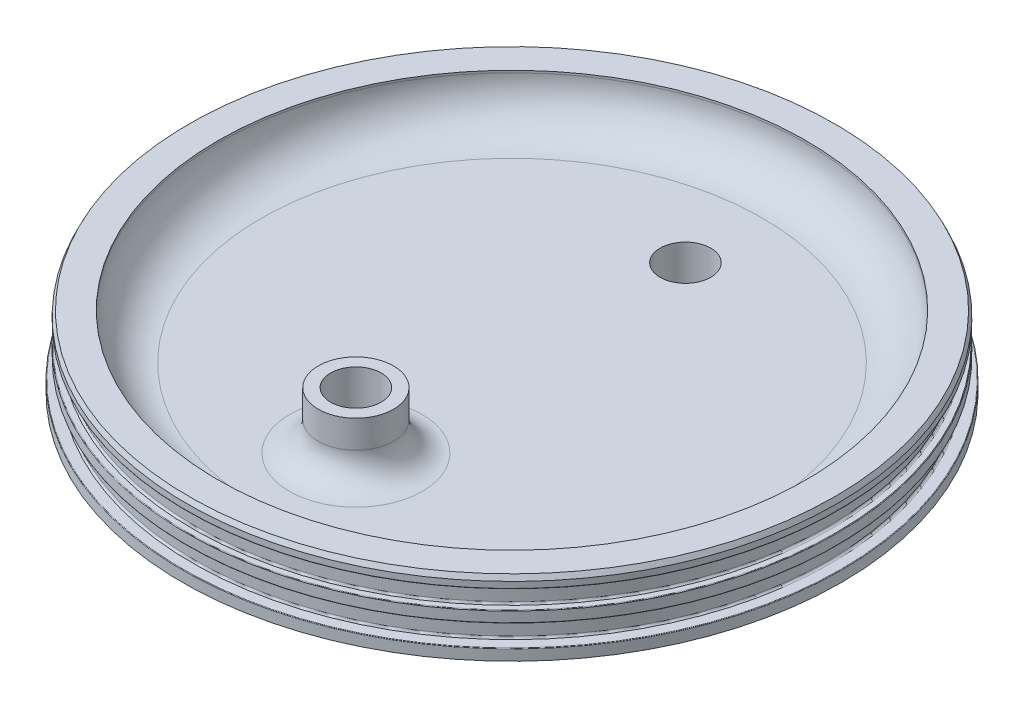
SolidWorks part; units mm, degrees
material "6061-T6 (SS)"
ref_plane "Front Plane" through (0, 0, 0) normal (0, 0, 1) x (1, 0, 0)
ref_plane "Top Plane" through (0, 0, 0) normal (0, 1, 0) x (1, 0, 0)
ref_plane "Right Plane" through (0, 0, 0) normal (1, 0, 0) x (0, 0, -1)
sketch "Sketch1" plane through (0, 0, 0) normal (0, 0, 1) x (1, 0, 0)
  line L0 (0, 48.1922) -> (0, -25.6743) construction
  line L1 (0, 0) -> (72.39, 0)
  line L2 (72.39, 0) -> (72.39, 2.4638)
  line L3 (72.39, 2.4638) -> (69.6468, 2.4638)
  line L4 (69.6468, 2.4638) -> (69.6468, 6.5278)
  line L5 (69.6468, 6.5278) -> (71.4248, 6.5278)
  line L6 (71.4248, 6.5278) -> (71.4248, 8.9916)
  line L7 (71.4248, 8.9916) -> (69.6468, 8.9916)
  line L8 (64.5668, 15.5956) -> (64.5668, 5.588)
  line L9 (64.5668, 5.588) -> (0, 5.588)
  line L10 (0, 5.588) -> (0, 0)
  line L11 (69.6468, 8.9916) -> (69.6468, 13.0556)
  line L12 (69.6468, 13.0556) -> (71.4248, 13.0556)
  line L13 (71.4248, 13.0556) -> (71.4248, 15.5956)
  line L14 (71.4248, 15.5956) -> (64.5668, 15.5956)
  dimension "D2" = 4.064
  dimension "D5" = 5.588
  dimension "D7" = 4.064
  dimension "D4" = 2.4638
  dimension "D8" = 2.54
  dimension "D6" = 5.08
  dimension "D1" = 72.39
  dimension "D9" = 1.778
  dimension "D3" = 69.6468
revolve "Revolve1" add sketch "Sketch1" angle 360 about L0
sketch "Sketch6" plane through (0, 0, 0) normal (0, -1, 0) x (1, 0, 0)
  circle A0 centre (0, 0) radius 66.04
  dimension "D1" = 132.08
extrude "Boss-Extrude1" add sketch "Sketch6" along normal blind 2.54
hole_wizard "Pipe Tap Drill for 1/4 Tap - GN2" positions "Sketch2" profile "Sketch3" hole size "1/4" standard "ANSI Inch" end condition through all
sketch "Sketch2" plane through (0, 5.588, 0) normal (0, 1, 0) x (1, 0, 0)
  point P4 (0, -34.29)
  dimension "D1" = 34.29
sketch "Sketch3" plane through (0, 5.588, 34.29) normal (1, 0, 0) x (0, 0, 1)
  line L0 (0, 0) -> (0, 8.128)
  line L1 (0, 8.128) -> (5.5626, 8.128)
  line L2 (5.5626, 8.128) -> (5.5626, 0)
  line L5 (5.5626, 0) -> (0, 0)
  line L11 (0, -6.35) -> (0, 107.95) construction
  dimension "Thru Hole Dia." = 11.1252
  dimension "Thru Hole Depth" = 8.128
fillet "CNC ID Fillet" radius 0.4064 5 edges at (-69.6468, 6.5278, 0) (-69.6468, 2.4638, 0) (-69.6468, 13.0556, 0) (-69.6468, 8.9916, 0) (66.04, 0, 0)
fillet "CNC OD Fillet" radius 0.127 5 edges at (-71.4248, 6.5278, 0) (-72.39, 2.4638, 0) (66.04, -2.54, 0) (-71.4248, 13.0556, 0) (-71.4248, 8.9916, 0)
chamfer "CNC Chamfers" distance 0.508 angle 65 1 edges at (-71.4248, 15.5956, 0) first distance on face at (-64.5668, 15.5956, 0)
hole_wizard "Pipe Tap Drill for 1/4 Tap - Relief Valve" positions "Sketch13" profile "Sketch14" hole size "1/4" standard "ANSI Inch" end condition through all
sketch "Sketch13" plane through (0, -2.54, 0) normal (0, -1, 0) x (-1, 0, 0)
  point P4 (0, 38.1)
  dimension "D1" = 38.1
sketch "Sketch14" plane through (0, -2.54, -38.1) normal (1, 0, 0) x (0, 0, -1)
  line L0 (0, 0) -> (0, 18.1356)
  line L1 (0, 18.1356) -> (5.5626, 18.1356)
  line L2 (5.5626, 18.1356) -> (5.5626, 0)
  line L5 (5.5626, 0) -> (0, 0)
  line L11 (0, -6.35) -> (0, 107.95) construction
  dimension "Thru Hole Dia." = 11.1252
  dimension "Thru Hole Depth" = 18.1356
sketch "Sketch15" plane through (0, -2.54, 0) normal (0, -1, 0) x (1, 0, 0)
  circle A0 centre (0, 34.29) radius 8.255
  circle A1 centre (0, 34.29) radius 5.5626 construction
  circle A2 centre (0, 34.29) radius 5.5626
  dimension "D1" = 16.51
extrude "Boss-Extrude2" add sketch "Sketch15" against normal blind 12.446 from surface starting at face at (5.5626, 5.588, -38.1)
fillet "Fillet2" radius 6.35 1 edges at (8.255, 5.588, 34.29)
fillet "Fillet3" radius 9.525 1 edges at (-64.5668, 5.588, 0)
sketch "Sketch16" plane through (0, -2.54, 0) normal (0, -1, 0) x (1, 0, 0)
  line L0 (0, 34.29) -> (0, -38.1) construction
  line L1 (25.4, 26.67) -> (-25.4, 26.67) construction
  line L2 (-9.4223, -1.905) -> (9.4223, -1.905) construction
  line L3 (25.4, -30.48) -> (-25.4, -30.48) construction
  text T0 "GN2"
  text T1 "VENT\r\n"
  point P7 (0, 26.67)
  point P14 (0, -1.905)
  dimension "D1" = 50.8
  dimension "D2" = 7.62
equation "\"D3@Sketch1\"=5.484/2"
equation "\"D1@Sketch1\"=5.7/2"
